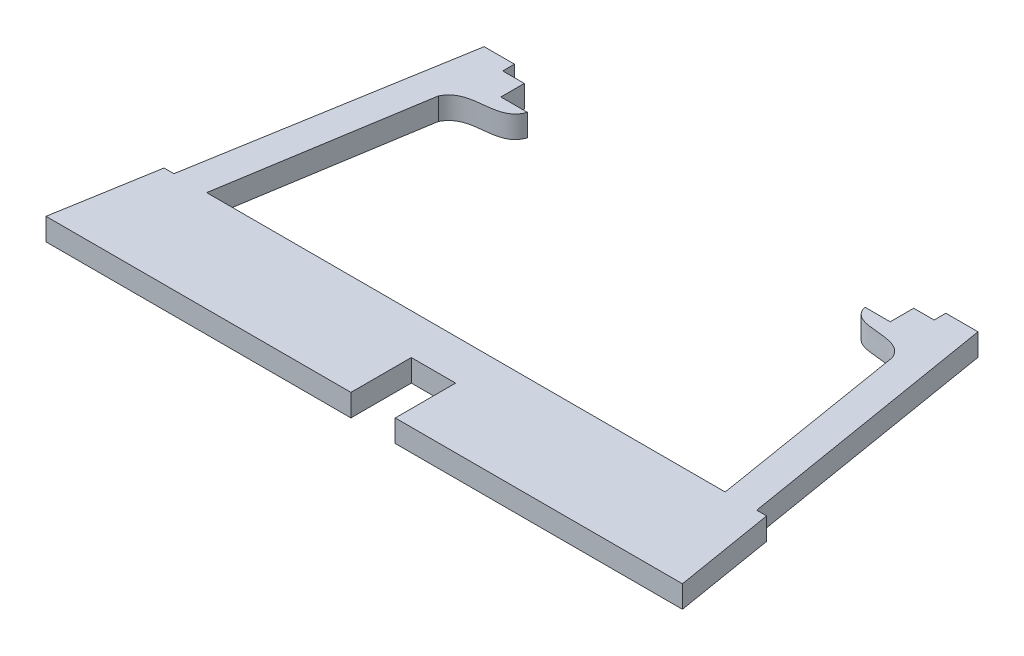
SolidWorks part; units mm, degrees
ref_plane "前视基准面" through (0, 0, 0) normal (0, 0, 1) x (1, 0, 0)
ref_plane "上视基准面" through (0, 0, 0) normal (0, 1, 0) x (1, 0, 0)
ref_plane "右视基准面" through (0, 0, 0) normal (1, 0, 0) x (0, 0, -1)
sketch "草图1" plane through (0, 0, 0) normal (0, 1, 0) x (1, 0, 0)
  line L0 (16.4072, 41.5203) -> (11.6078, 41.5203)
  line L1 (11.6078, 41.5203) -> (11.6078, 45.7617)
  line L2 (11.6078, 45.7617) -> (7.7014, 45.7617)
  line L3 (7.7014, 45.7617) -> (7.7014, 47.8823)
  line L4 (7.7014, 47.8823) -> (2.2323, 47.8823)
  line L5 (2.2323, 47.8823) -> (-5.9155, 0)
  line L6 (-5.9155, 0) -> (-7.7014, 0)
  line L7 (-7.7014, 0) -> (-10.8007, -18.2141)
  line L8 (-10.8007, -18.2141) -> (44.2685, -18.2141)
  line L9 (44.2685, -18.2141) -> (44.2685, -7.3141)
  line L10 (44.2685, -7.3141) -> (52.2685, -7.3141)
  line L11 (52.2685, -7.3141) -> (52.2685, -18.2141)
  line L12 (52.2685, -18.2141) -> (104.1357, -18.2141)
  line L13 (104.1357, -18.2141) -> (101.1221, 0)
  line L14 (101.1221, 0) -> (99.3363, 0)
  line L15 (99.3363, 0) -> (91.414, 47.8823)
  line L16 (91.414, 47.8823) -> (85.6078, 47.8823)
  line L17 (85.6078, 47.8823) -> (85.6078, 45.7617)
  line L18 (85.6078, 45.7617) -> (81.9245, 45.7617)
  line L19 (81.9245, 45.7617) -> (81.9245, 41.5203)
  line L20 (81.9245, 41.5203) -> (77.3484, 41.5203)
  line L21 (5.8039, 36.0513) -> (0, 0)
  line L22 (0, 0) -> (93.644, 0)
  line L23 (93.644, 0) -> (87.7285, 36.0513)
  spline S0 degree 3 poles (16.4072, 41.5203) (14.7613, 36.946) (8.0572, 40.4772) (5.8039, 36.0513) knots 0 0 0 0 1 1 1 1
  spline S1 degree 3 poles (77.3484, 41.5203) (78.5308, 36.8864) (85.8527, 40.7149) (87.7285, 36.0513) knots 0 0 0 0 1 1 1 1
  dimension "D1" = 8
  dimension "D2" = 10.9
extrude "凸台-拉伸1" add sketch "草图1" along normal blind 4
